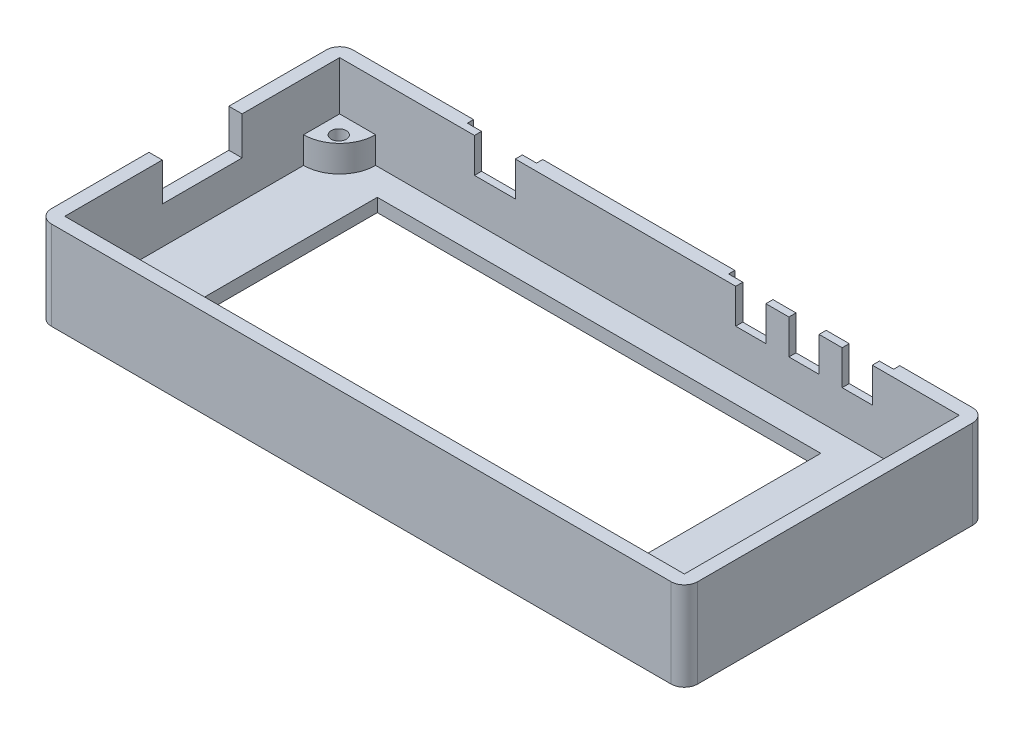
SolidWorks part; units mm, degrees
note: The reader was unsure of these and kept them because the rebuilt part matched: shared geometry of "草图1<6>", "草图1<7>", "草图5<6>".
ref_plane "前视基准面" through (0, 0, 0) normal (0, 0, 1) x (1, 0, 0)
ref_plane "上视基准面" through (0, 0, 0) normal (0, 1, 0) x (1, 0, 0)
ref_plane "右视基准面" through (0, 0, 0) normal (1, 0, 0) x (0, 0, -1)
sketch "草图1" plane through (0, 0, 0) normal (0, 1, 0) x (1, 0, 0)
  line L1 (-34.9275, 15.494) -> (34.9275, 15.494)
  line L2 (-34.9275, 15.494) -> (-34.9275, -15.494)
  line L4 (34.9275, 15.494) -> (34.9275, -15.494)
  line L5 (-34.9275, 15.494) -> (34.9275, -15.494) construction
  line L6 (-34.9275, -15.494) -> (34.9275, 15.494) construction
  line L9 (-34.9275, -15.494) -> (34.9275, -15.494)
  line L12 (-30.8635, -15.494) -> (-30.8635, 15.494) construction
  line L13 (29.7365, 15.494) -> (29.7365, -15.494) construction
  line L14 (-27.6635, 12.478) -> (-27.6635, -12.478)
  line L15 (22.3365, 12.478) -> (22.3365, -12.478)
  line L16 (0, 15.494) -> (0, -15.494) construction
  line L17 (-34.9275, 0) -> (34.9275, 0) construction
  line L18 (-27.6635, 12.478) -> (22.3365, 12.478)
  line L19 (-27.6635, -12.478) -> (22.3365, -12.478)
  arc A0 (-34.9275, -11.43) -> (-30.8635, -15.494) centre (-34.9275, -15.494) cw
  arc A1 (-34.9275, 11.43) -> (-30.8635, 15.494) centre (-34.9275, 15.494) ccw
  arc A3 (34.9275, -10.43) -> (29.8635, -15.494) centre (34.9275, -15.494) ccw
  arc A4 (34.9275, 10.43) -> (29.8635, 15.494) centre (34.9275, 15.494) cw
  point P0 (0, 0)
  point P3 (0, 0)
  point P9 (0, 0)
  point P16 (0, 0)
  point P18 (0, 0)
  point P26 (0, 0)
  point P27 (0, 0)
  point P28 (0, 0)
  point P29 (0, 0)
  point P30 (0, 0)
  point P32 (0, 0)
  dimension "D4" = 4.064
  dimension "D5" = 4.064
  dimension "D6" = 5.064
  dimension "D1" = 30.988
  dimension "D2" = 69.855
  dimension "D7" = 5.191
  dimension "D8" = 3.2
  dimension "D9" = 7.4
  dimension "D10" = 24.956
extrude "凸台-拉伸1" add sketch "草图1" along normal blind 1.5 contours L4 L9 L2 L1
extrude "切除-拉伸2" cut sketch "草图1<6>" along normal up to next contours L14 L19 L15 L18
sketch "草图1<6>" plane through (0, 0, 0) normal (0, 1, 0) x (1, 0, 0) same geometry as "草图1"
extrude "拉伸-薄壁1" add sketch "草图1<7>" along normal blind 10 separate body thin contours L4 L9 L2 L1 thin type one direction wall 1.5
sketch "草图1<7>" plane through (0, 0, 0) normal (0, 1, 0) x (1, 0, 0) same geometry as "草图1"
fillet "圆角1" radius 1.5 4 edges at (36.4275, 5, -16.994) (36.4275, 5, 16.994) (-36.4275, 5, 16.994) (-36.4275, 5, -16.994)
sketch "草图2" plane through (0, 1.5, 0) normal (0, 1, 0) x (1, 0, 0)
  line L2 (-34.9275, -11.43) -> (-34.9275, -15.494)
  line L3 (-34.9275, -15.494) -> (-30.8635, -15.494)
  line L4 (-30.8635, 15.494) -> (-34.9275, 15.494)
  line L5 (-34.9275, 15.494) -> (-34.9275, 11.43)
  line L7 (29.8635, 15.494) -> (34.9275, 15.494)
  line L8 (34.9275, 15.494) -> (34.9275, 10.43)
  line L9 (34.9275, -10.43) -> (34.9275, -15.494)
  line L10 (34.9275, -15.494) -> (29.8635, -15.494)
  arc A0 (29.8635, 15.494) -> (34.9275, 10.43) centre (34.9275, 15.494) ccw construction
  arc A1 (34.9275, -10.43) -> (29.8635, -15.494) centre (34.9275, -15.494) ccw construction
  arc A2 (-30.8635, -15.494) -> (-34.9275, -11.43) centre (-34.9275, -15.494) ccw construction
  arc A3 (-34.9275, 11.43) -> (-30.8635, 15.494) centre (-34.9275, 15.494) ccw construction
  arc A4 (29.8635, 15.494) -> (34.9275, 10.43) centre (34.9275, 15.494) ccw
  arc A5 (34.9275, -10.43) -> (29.8635, -15.494) centre (34.9275, -15.494) ccw
  arc A6 (-30.8635, -15.494) -> (-34.9275, -11.43) centre (-34.9275, -15.494) ccw
  arc A7 (-34.9275, 11.43) -> (-30.8635, 15.494) centre (-34.9275, 15.494) ccw
  point P6 (0, 0)
extrude "凸台-拉伸2" add sketch "草图2" along normal blind 3
sketch "草图3" plane through (0, 4.5, 0) normal (0, 1, 0) x (1, 0, 0)
  line L0 (34.9275, 15.494) -> (34.9275, -15.494) construction
  line L2 (34.9275, 10.43) -> (34.9275, 15.494) construction
  line L3 (-34.9275, -17.526) -> (34.9275, -17.526) construction
  line L6 (-34.9275, -15.494) -> (34.9275, -15.494) construction
  line L7 (-34.9275, 15.494) -> (-34.9275, -15.494) construction
  line L10 (0, 15.494) -> (0, -15.494) construction
  line L11 (-34.9275, 0) -> (34.9275, 0) construction
  line L12 (0, 15.494) -> (0, -15.494) construction
  line L13 (-34.9275, 0) -> (34.9275, 0) construction
  circle A2 centre (-32.9275, -13.394) radius 0.85
  circle A3 centre (-32.9275, 13.394) radius 0.85
  circle A4 centre (31.9275, -13.394) radius 0.85
  circle A5 centre (31.9275, 13.394) radius 0.85
  dimension "D2" = 0.85
  dimension "D6" = 0.85
  dimension "D1" = 2.1
  dimension "D3" = 2
  dimension "D4" = 3
  dimension "D5" = 2.1
sketch "草图4" plane through (-34.9275, 0, 0) normal (1, 0, 0) x (0, 0, -1)
  line L0 (-11.43, 4.5) -> (11.43, 4.5) construction
  line L2 (-4.5, 10) -> (4.5, 10)
  line L3 (-4.5, 10) -> (-4.5, 5.7)
  line L4 (-4.5, 5.7) -> (4.5, 5.7)
  line L5 (4.5, 10) -> (4.5, 5.7)
  point P8 (0, 5.7)
  point P10 (0, 0)
  point P11 (-11.26, 4.5)
  point P13 (0, 0)
  point P14 (11.3829, 4.5)
  dimension "D1" = 1.2
  dimension "D2" = 4.3
  dimension "D3" = 9
extrude "切除-拉伸3" cut sketch "草图4" against normal up to next contours L3 L2 L5 L4
sketch "草图5" plane through (0, 0, -15.494) normal (0, 0, 1) x (1, 0, 0)
  line L0 (-30.8635, 4.5) -> (29.8635, 4.5) construction
  line L1 (15.7275, 10.1) -> (15.7275, 6.1)
  line L3 (-19.7275, 10.1) -> (-15.1275, 10.1)
  line L4 (-19.7275, 10.1) -> (-19.7275, 6.1)
  line L5 (-19.7275, 6.1) -> (-15.1275, 6.1)
  line L6 (-15.1275, 10.1) -> (-15.1275, 6.1)
  line L11 (-21.3275, 11.7) -> (-21.3275, 4.5)
  line L12 (-21.3275, 4.5) -> (-13.5275, 4.5)
  line L13 (-13.5275, 11.7) -> (-13.5275, 4.5)
  line L14 (-21.3275, 11.7) -> (-13.5275, 11.7)
  line L15 (34.9275, 10) -> (34.9275, 4.5) construction
  line L16 (21.7275, 10.1) -> (25.1275, 10.1)
  line L17 (21.7275, 10.1) -> (21.7275, 6.1)
  line L18 (21.7275, 6.1) -> (25.1275, 6.1)
  line L19 (25.1275, 10.1) -> (25.1275, 6.1)
  line L24 (8.1275, 11.7) -> (8.1275, 4.5)
  line L25 (8.1275, 4.5) -> (26.7275, 4.5)
  line L26 (26.7275, 11.7) -> (26.7275, 4.5)
  line L27 (8.1275, 11.7) -> (26.7275, 11.7)
  line L28 (15.7275, 10.1) -> (19.1275, 10.1)
  line L29 (19.1275, 10.1) -> (19.1275, 6.1)
  line L30 (15.7275, 6.1) -> (19.1275, 6.1)
  line L31 (9.7275, 10.1) -> (9.7275, 6.1)
  line L32 (9.7275, 10.1) -> (13.1275, 10.1)
  line L33 (13.1275, 10.1) -> (13.1275, 6.1)
  line L34 (9.7275, 6.1) -> (13.1275, 6.1)
  line L35 (21.7275, 10.1) -> (15.7275, 10.1) construction
  line L39 (-34.9275, 10) -> (-34.9275, 0) construction
  point P2 (-17.4275, 6.1)
  point P21 (23.4275, 6.1)
  point P38 (-34.3438, 4.019)
  dimension "D2" = 4.6
  dimension "D3" = 4
  dimension "D4" = 1.6
  dimension "D6" = 3.4
  dimension "D7" = 4
  dimension "D8" = 11.5
  dimension "D9" = 1.6
  dimension "D12" = 6
  dimension "D10" = 1.6
  dimension "D13" = 1.6
  dimension "D14" = 1.6
  dimension "D15" = 1.6
  dimension "D16" = 17.5
  dimension "D5" = 1.6
  dimension "D11" = 3
extrude "切除-拉伸4" cut sketch "草图5" against normal up to next contours L31 L34 L33 L32 | L1 L30 L29 L28 | L19 L16 L17 L18 | L4 L3 L6 L5
extrude "切除-拉伸6" cut sketch "草图5<6>" along normal blind 0.7 from surface at -1.5 contours L14 L13 L12 L11 | L27 L26 L25 L24 starting at face at (6.971, 7.44, -16.994)
sketch "草图5<6>" plane through (0, 0, -15.494) normal (0, 0, 1) x (1, 0, 0) same geometry as "草图5"
extrude "切除-拉伸7" cut sketch "草图3" against normal up to surface (3 mm away) up to face at (-2.6635, 1.5, 0)
